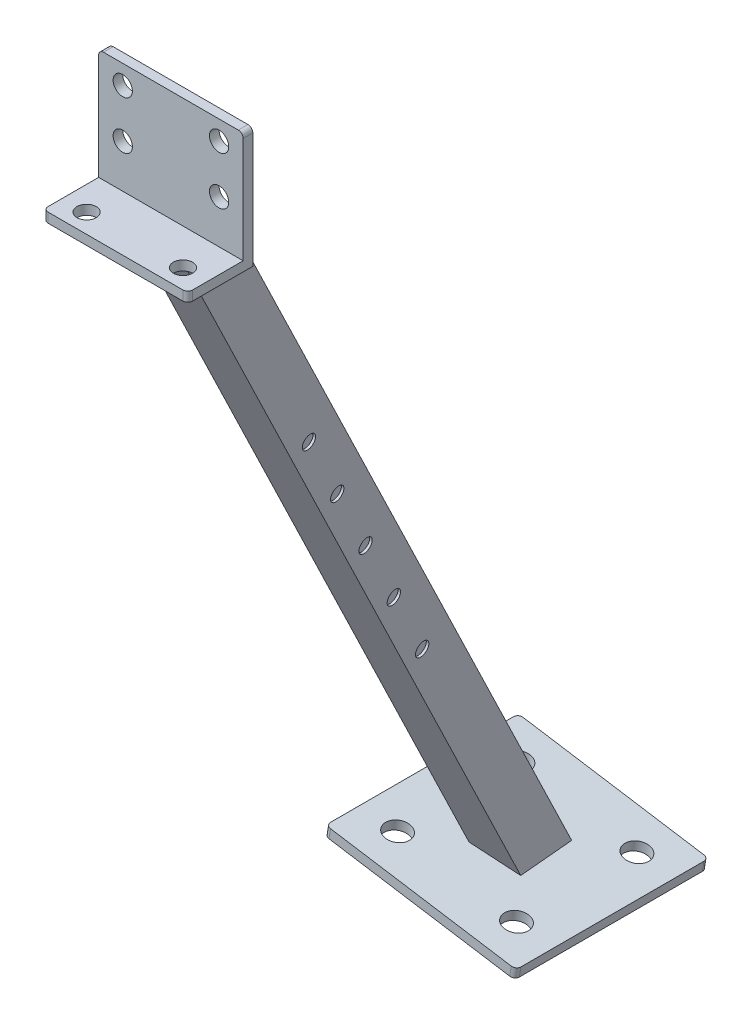
SolidWorks part; units mm, degrees
ref_plane "Front Plane" through (0, 0, 0) normal (0, 0, 1) x (1, 0, 0)
ref_plane "Top Plane" through (0, 0, 0) normal (0, 1, 0) x (1, 0, 0)
ref_plane "Right Plane" through (0, 0, 0) normal (1, 0, 0) x (0, 0, -1)
sketch "Sketch1" plane through (0, 0, 0) normal (1, 0, 0) x (0, 0, -1)
  line L0 (0, 0) -> (0, 50)
  line L1 (0, 50) -> (-4, 50)
  line L2 (-4, 50) -> (-4, 4)
  line L3 (-4, 4) -> (-27, 4)
  line L4 (-27, 4) -> (-27, 0)
  line L5 (-27, 0) -> (0, 0)
  dimension "D1" = 4
  dimension "D2" = 4
  dimension "D3" = 27
  dimension "D4" = 50
extrude "Boss-Extrude1" add sketch "Sketch1" along normal blind 60
ref_plane "Plane1" through (0, 0, 0) normal (0, -0.866, -0.5) x (-1, 0, 0)
sketch "Sketch2" plane through (0, 0, 0) normal (0, -0.866, -0.5) x (-1, 0, 0)
  line L0 (-30, 0) -> (-30, -23.3827)
  line L1 (-60, 0) -> (0, 0) construction
  line L2 (-60, -23.3827) -> (0, -23.3827) construction
ref_plane "Plane2" through (0.7342, 4.0142, 2.3176) normal (-0.1564, -0.8554, -0.4938) x (0, -0.5, 0.866)
sketch "Sketch3" plane through (0.7342, 4.0142, 2.3176) normal (-0.1564, -0.8554, -0.4938) x (0, -0.5, 0.866)
  line L0 (-9, -38.6307) -> (-9, -20.6307)
  line L1 (10, -39.6307) -> (-10, -39.6307)
  line L2 (10, -39.6307) -> (10, -19.6307)
  line L3 (10, -19.6307) -> (-10, -19.6307)
  line L4 (-10, -39.6307) -> (-10, -19.6307)
  line L5 (10, -39.6307) -> (-10, -19.6307) construction
  line L6 (10, -19.6307) -> (-10, -39.6307) construction
  line L7 (9, -20.6307) -> (-9, -20.6307)
  line L8 (9, -38.6307) -> (9, -20.6307)
  line L9 (9, -38.6307) -> (-9, -38.6307)
  point P0 (0, -29.6307)
  dimension "D1" = 20
  dimension "D2" = 20
  dimension "D3" = 1
extrude "Boss-Extrude2" add sketch "Sketch3" along normal blind 500 and the other way blind 20
sketch "Sketch5" plane through (0, 0, 0) normal (-1, 0, 0) x (0, 0, 1)
  line L0 (4, 4) -> (4, 36.0549)
  line L1 (4, 50) -> (4, 4) construction
  line L2 (4, 36.0549) -> (38.7814, 4)
  line L3 (4, 4) -> (27, 4) construction
  line L4 (38.7814, 4) -> (4, 4)
extrude "Cut-Extrude1" cut sketch "Sketch5" against normal blind 60
ref_plane "Plane3" through (-56.757, -358.3494, 0) normal (0.1564, 0.9877, 0) x (0.9877, -0.1564, 0)
sketch "Sketch7" plane through (-56.757, -358.3494, 0) normal (0.1564, 0.9877, 0) x (0.9877, -0.1564, 0)
  line L0 (19.2115, 0) -> (8.5312, 254.8002) construction
  line L1 (8.5312, 254.8002) -> (28.4656, 256.3645) construction
  line L3 (60.6025, 165.5937) -> (-19.3975, 165.5937)
  line L4 (60.6025, 165.5937) -> (60.6025, 245.5937)
  line L5 (60.6025, 245.5937) -> (-19.3975, 245.5937)
  line L6 (-19.3975, 165.5937) -> (-19.3975, 245.5937)
  line L7 (60.6025, 165.5937) -> (-19.3975, 245.5937) construction
  line L8 (60.6025, 245.5937) -> (-19.3975, 165.5937) construction
  point P0 (20.6025, 205.5937)
  point P5 (20.6025, 205.5937)
  dimension "D1" = 10
  dimension "D2" = 50
  dimension "D3" = 80
  dimension "D4" = 80
extrude "Boss-Extrude3" add sketch "Sketch7" along normal blind 4
sketch "Sketch8" plane through (-56.757, -358.3494, 0) normal (-0.1564, -0.9877, 0) x (0.9877, -0.1564, 0)
  line L1 (-25.4737, -284.3403) -> (70.9138, -284.3403)
  line L2 (-25.4737, -284.3403) -> (-25.4737, -180.2822)
  line L3 (-25.4737, -180.2822) -> (70.9138, -180.2822)
  line L4 (70.9138, -284.3403) -> (70.9138, -180.2822)
  line L5 (-25.4737, -284.3403) -> (70.9138, -180.2822) construction
  line L6 (-25.4737, -180.2822) -> (70.9138, -284.3403) construction
  point P0 (22.72, -232.3112)
extrude "Cut-Extrude3" cut sketch "Sketch8" along normal blind 100
sketch "Sketch9" plane through (0, 0, 0) normal (0, 0, -1) x (-1, 0, 0)
  circle A0 centre (-50, 22) radius 4 construction
  circle A1 centre (-10, 22) radius 4 construction
  circle A2 centre (-10, 42) radius 4 construction
  circle A3 centre (-50, 42) radius 4 construction
  circle A4 centre (-50, 22) radius 4
  circle A5 centre (-10, 22) radius 4
  circle A6 centre (-10, 42) radius 4
  circle A7 centre (-50, 42) radius 4
extrude "Cut-Extrude4" cut sketch "Sketch9" against normal up to next
sketch "Sketch10" plane through (0, 0, 0) normal (0, -1, 0) x (1, 0, 0)
  circle A0 centre (50, 19) radius 4 construction
  circle A1 centre (10, 19) radius 4 construction
  circle A2 centre (50, 19) radius 4
  circle A3 centre (10, 19) radius 4
extrude "Cut-Extrude5" cut sketch "Sketch10" against normal up to next
sketch "Sketch11" plane through (-56.757, -358.3494, 0) normal (-0.1564, -0.9877, 0) x (0.9877, -0.1564, 0)
  line L0 (-19.3975, -165.5937) -> (60.6025, -165.5937) construction
  line L1 (-19.3975, -245.5937) -> (-19.3975, -165.5937) construction
  circle A0 centre (-4.3975, -180.5937) radius 5
  circle A1 centre (45.6025, -180.5937) radius 5
  circle A2 centre (45.6025, -230.5937) radius 5
  circle A3 centre (-4.3975, -230.5937) radius 5
  dimension "D1" = 10
  dimension "D4" = 2
  dimension "D2" = 15
  dimension "D3" = 15
  dimension "D5" = 2
extrude "Cut-Extrude6" cut sketch "Sketch11" against normal up to next
fillet "Fillet1" radius 2 4 edges at (60, 2, 27) (0, 2, 27) (0, 50, 2) (60, 50, 2)
fillet "Fillet2" radius 2 4 edges at (3.4123, -365.8544, -245.5937) (-75.6028, -353.3396, -245.5937) (3.4123, -365.8544, -165.5937) (-75.6028, -353.3396, -165.5937)
sketch "Sketch12" plane through (19.389, -2.6595, -1.5355) normal (-0.9877, 0.1355, 0.0782) x (0.0775, -0.0106, 0.9969)
  ellipse E0 centre (-61.2259, -111.9955) end of major axis (-60.456, -109.0959) minor radius 2.9902 construction
  ellipse E1 centre (-78.5072, -142.423) end of major axis (-77.7373, -139.5235) minor radius 2.9902 construction
  ellipse E2 centre (-95.7885, -172.8505) end of major axis (-95.0186, -169.951) minor radius 2.9902 construction
  ellipse E3 centre (-113.0698, -203.2781) end of major axis (-112.2999, -200.3785) minor radius 2.9902 construction
  ellipse E4 centre (-130.3511, -233.7056) end of major axis (-129.5813, -230.8061) minor radius 2.9902 construction
  ellipse E5 centre (-61.2259, -111.9955) end of major axis (-60.456, -109.0959) minor radius 2.9902
  ellipse E6 centre (-78.5072, -142.423) end of major axis (-77.7373, -139.5235) minor radius 2.9902
  ellipse E7 centre (-95.7885, -172.8505) end of major axis (-95.0186, -169.951) minor radius 2.9902
  ellipse E8 centre (-113.0698, -203.2781) end of major axis (-112.2999, -200.3785) minor radius 2.9902
  ellipse E9 centre (-130.3511, -233.7056) end of major axis (-129.5813, -230.8061) minor radius 2.9902
extrude "Cut-Extrude7" cut sketch "Sketch12" against normal through all
